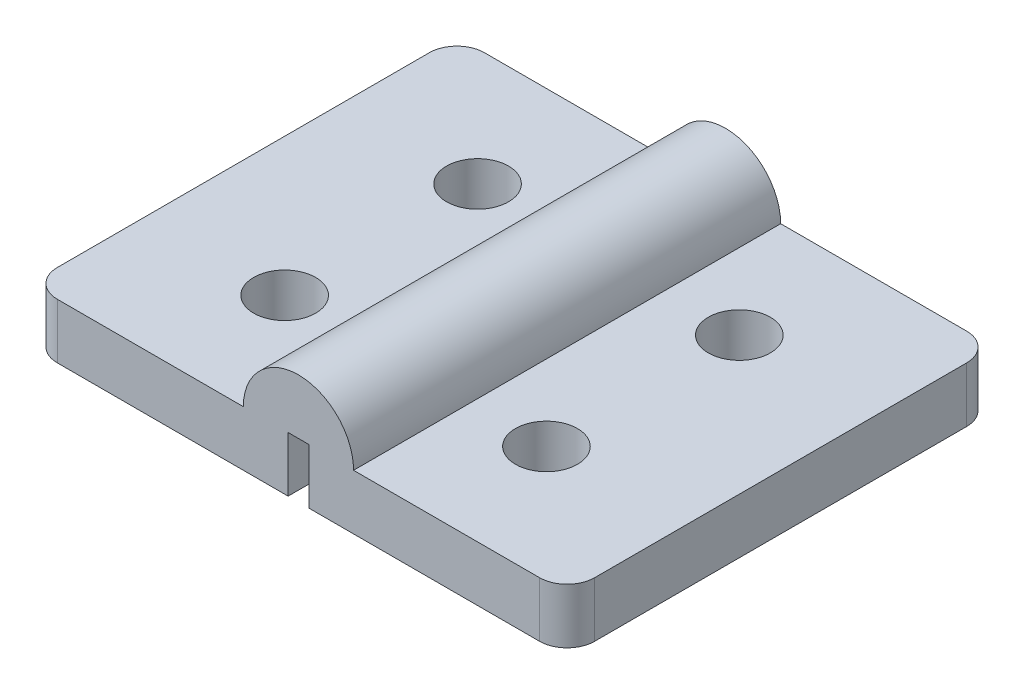
SolidWorks part; units mm, degrees
ref_plane "Alzado" through (0, 0, 0) normal (0, 0, 1) x (1, 0, 0)
ref_plane "Planta" through (0, 0, 0) normal (0, 1, 0) x (1, 0, 0)
ref_plane "Vista lateral" through (0, 0, 0) normal (1, 0, 0) x (0, 0, -1)
sketch "Croquis1" plane through (0, 0, 0) normal (0, 1, 0) x (1, 0, 0)
  line L1 (0, 0) -> (39, 0)
  line L2 (0, 0) -> (0, 31)
  line L3 (0, 31) -> (39, 31)
  line L4 (39, 0) -> (39, 31)
  line L5 (10, 22.5) -> (29, 22.5) construction
  line L6 (10, 22.5) -> (10, 8.5) construction
  line L7 (10, 8.5) -> (29, 8.5) construction
  line L8 (29, 22.5) -> (29, 8.5) construction
  circle A0 centre (10, 22.5) radius 2.25
  circle A1 centre (29, 22.5) radius 2.25
  circle A2 centre (29, 8.5) radius 2.25
  circle A3 centre (10, 8.5) radius 2.25
  dimension "D7" = 4.5
  dimension "D1" = 39
  dimension "D2" = 31
  dimension "D3" = 14
  dimension "D4" = 19
  dimension "D5" = 10
  dimension "D6" = 8.5
extrude "Saliente-Extruir1" add sketch "Croquis1" along normal blind 4
sketch "Croquis2" plane through (0, 0, 0) normal (0, 0, 1) x (1, 0, 0)
  line L0 (19.5, 4) -> (19.5, 0) construction
  line L1 (0, 4) -> (39, 4) construction
  line L2 (0, 0) -> (39, 0) construction
  circle A0 centre (19.5, 4) radius 4
  dimension "D1" = 8
extrude "Saliente-Extruir2" add sketch "Croquis2" against normal up to surface (31 mm away) up to face at (19.5, 2, -31)
sketch "Croquis3" plane through (0, 0, -31) normal (0, 0, -1) x (-1, 0, 0)
  line L0 (-19.5, 0) -> (-19.5, 8) construction
  line L1 (-39, 0) -> (0, 0) construction
  line L3 (-18.75, 0) -> (-20.25, 0)
  line L4 (-18.75, 0) -> (-18.75, 4)
  line L5 (-18.75, 4) -> (-20.25, 4)
  line L6 (-20.25, 0) -> (-20.25, 4)
  arc A0 (-15.5, 4) -> (-23.5, 4) centre (-19.5, 4) ccw construction
  dimension "D1" = 1.5
  dimension "D2" = 0.75
  dimension "D3" = 4
extrude "Cortar-Extruir1" cut sketch "Croquis3" against normal up to surface (31 mm away) up to face at (19.5, 3.3333, 0)
fillet "Redondeo1" radius 2 4 edges at (39, 2, -31) (39, 2, 0) (0, 2, 0) (0, 2, -31)
